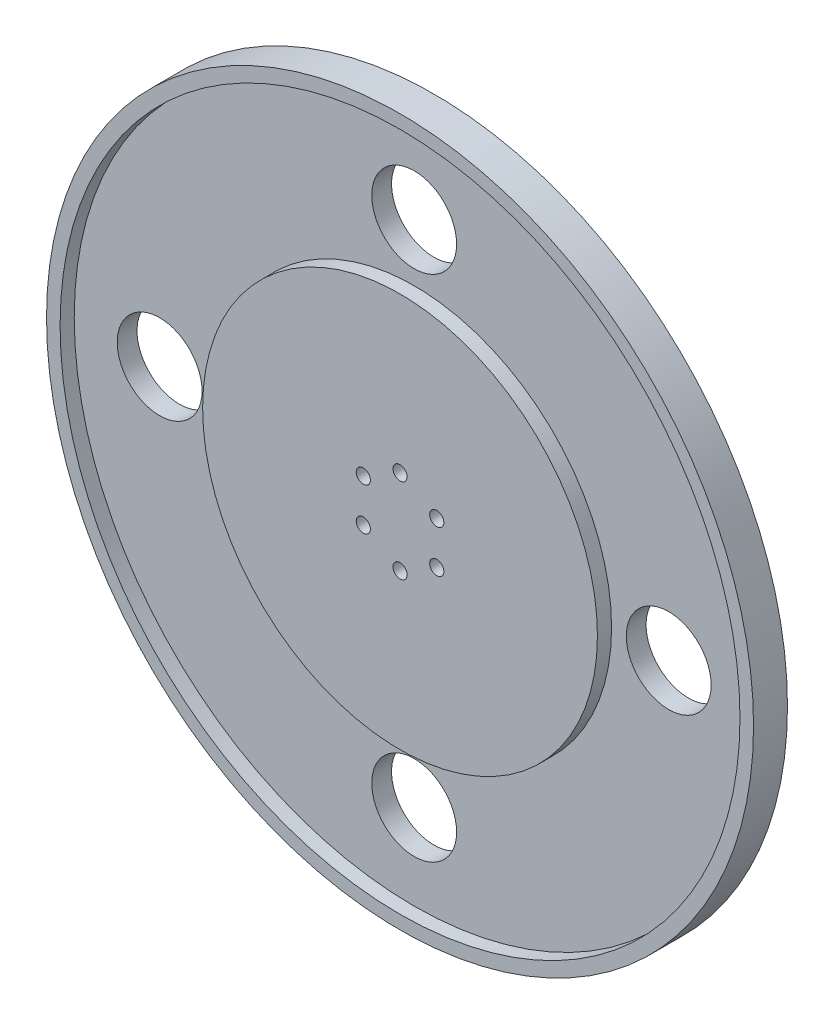
SolidWorks part; units mm, degrees
ref_plane "Front Plane" through (0, 0, 0) normal (0, 0, 1) x (1, 0, 0)
ref_plane "Top Plane" through (0, 0, 0) normal (0, 1, 0) x (1, 0, 0)
ref_plane "Right Plane" through (0, 0, 0) normal (1, 0, 0) x (0, 0, -1)
sketch "Sketch1" plane through (0, 0, 0) normal (0, 0, 1) x (1, 0, 0)
  circle A0 centre (0, 0) radius 79.375
  circle A1 centre (0, 0) radius 76.327
  circle A2 centre (0, 0) radius 44.323
  dimension "D1" = 158.75
  dimension "D2" = 152.654
  dimension "D3" = 88.646
extrude "Boss-Extrude1" add sketch "Sketch1" along normal blind 7.62 contours A2 | A0 A1 region at (-77.1299, 0, 0) region at (0, 0, 0)
extrude "Boss-Extrude2" add sketch "Sketch1<3>" along normal blind 4.445 contours A1 A2 region at (-74.1681, 0, 0)
sketch "Sketch1<3>" plane through (0, 0, 0) normal (0, 0, 1) x (1, 0, 0) same geometry as "Sketch1"
sketch "Sketch2" plane through (0, 0, 7.62) normal (0, 0, 1) x (1, 0, 0)
  arc A0 (-1.582, 9.3927) -> (-7.3433, 6.0664) centre (0, 0) ccw
  circle A1 centre (0, 9.525) radius 1.5875
  circle A2 centre (8.2489, 4.7625) radius 1.5875
  circle A3 centre (8.2489, -4.7625) radius 1.5875
  circle A4 centre (0, -9.525) radius 1.5875
  circle A5 centre (-8.2489, -4.7625) radius 1.5875
  circle A6 centre (-8.2489, 4.7625) radius 1.5875
  arc A7 (7.3433, 6.0664) -> (1.582, 9.3927) centre (0, 0) ccw
  arc A8 (8.9253, -3.3263) -> (8.9253, 3.3263) centre (0, 0) ccw
  arc A9 (1.582, -9.3927) -> (7.3433, -6.0664) centre (0, 0) ccw
  arc A10 (-7.3433, -6.0664) -> (-1.582, -9.3927) centre (0, 0) ccw
  arc A11 (-8.9253, 3.3263) -> (-8.9253, -3.3263) centre (0, 0) ccw
  point P17 (0, 0)
  dimension "D1" = 19.05
  dimension "D2" = 3.175
  dimension "D3" = 6
extrude "Cut-Extrude1" cut sketch "Sketch2" against normal up to next contours A1 | A2 | A3 | A4 | A5 | A6 region at (0, 9.525, 7.62) region at (-8.2489, 4.7625, 7.62) region at (8.2489, 4.7625, 7.62) region at (-8.2489, -4.7625, 7.62) region at (8.2489, -4.7625, 7.62) region at (0, -9.525, 7.62)
sketch "Sketch3" plane through (0, 0, 4.445) normal (0, 0, 1) x (1, 0, 0)
  circle A0 centre (0, 0) radius 57.15
  circle A1 centre (0, 57.15) radius 9.525
  circle A2 centre (57.15, 0) radius 9.525
  circle A3 centre (0, -57.15) radius 9.525
  circle A4 centre (-57.15, 0) radius 9.525
  point P14 (0, 0)
  dimension "D1" = 114.3
  dimension "D2" = 19.05
  dimension "D3" = 4
extrude "Cut-Extrude2" cut sketch "Sketch3" against normal up to next contours A0 A1 | A0 A1 | A0 A2 | A0 A2 | A0 A3 | A0 A3 | A0 A4 | A0 A4 region at (52.9679, 0, 4.445) region at (61.0462, 0, 4.445) region at (0, 52.9679, 4.445) region at (0, 61.0462, 4.445) region at (0, -61.0462, 4.445) region at (0, -52.9679, 4.445) region at (-52.9679, 0, 4.445) region at (-61.0462, 0, 4.445)
